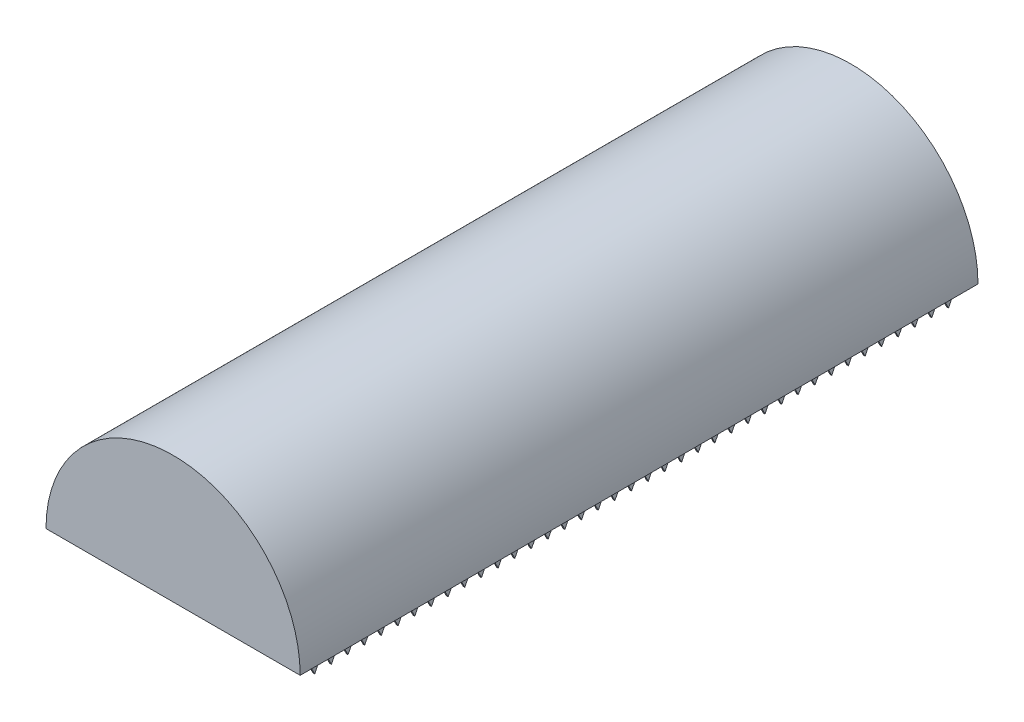
SolidWorks part; units mm, degrees
ref_plane "Front Plane" through (0, 0, 0) normal (0, 0, 1) x (1, 0, 0)
ref_plane "Top Plane" through (0, 0, 0) normal (0, 1, 0) x (1, 0, 0)
ref_plane "Right Plane" through (0, 0, 0) normal (1, 0, 0) x (0, 0, -1)
sketch "Sketch1" plane through (0, 0, 0) normal (0, 0, 1) x (1, 0, 0)
  line L0 (-76.2, 0) -> (76.2, 0)
  arc A0 (-76.2, 0) -> (76.2, 0) centre (0, 0) cw
  dimension "D1" = 76.2
extrude "Boss-Extrude1" add sketch "Sketch1" along normal blind 406.4
shell "Shell1" thickness 6.35 removed face at (0, 0, 203.2)
ref_plane "Plane1" through (69.85, 0, 0) normal (1, 0, 0) x (0, 0, -1)
sketch "Sketch3" plane through (69.85, 0, 0) normal (1, 0, 0) x (0, 0, -1)
  line L0 (-6.35, 0) -> (-11.35, -10)
  line L1 (-11.35, -10) -> (-16.35, 0)
  line L2 (-400.05, 0) -> (-6.35, 0) construction
  line L3 (-11.35, -10) -> (-11.35, 0) construction
  line L4 (-6.35, 0) -> (-16.35, 0) construction
  line L5 (-16.35, 0) -> (-21.35, -10)
  line L6 (-21.35, -10) -> (-26.35, 0)
  line L7 (-16.35, 0) -> (-26.35, 0) construction
  line L8 (-26.35, 0) -> (-31.35, -10)
  line L9 (-31.35, -10) -> (-36.35, 0)
  line L10 (-26.35, 0) -> (-36.35, 0) construction
  line L11 (-36.35, 0) -> (-41.35, -10)
  line L12 (-41.35, -10) -> (-46.35, 0)
  line L13 (-36.35, 0) -> (-46.35, 0) construction
  line L14 (-46.35, 0) -> (-51.35, -10)
  line L15 (-51.35, -10) -> (-56.35, 0)
  line L16 (-46.35, 0) -> (-56.35, 0) construction
  line L17 (-56.35, 0) -> (-61.35, -10)
  line L18 (-61.35, -10) -> (-66.35, 0)
  line L19 (-56.35, 0) -> (-66.35, 0) construction
  line L20 (-66.35, 0) -> (-71.35, -10)
  line L21 (-71.35, -10) -> (-76.35, 0)
  line L22 (-66.35, 0) -> (-76.35, 0) construction
  line L23 (-76.35, 0) -> (-81.35, -10)
  line L24 (-81.35, -10) -> (-86.35, 0)
  line L25 (-76.35, 0) -> (-86.35, 0) construction
  line L26 (-86.35, 0) -> (-91.35, -10)
  line L27 (-91.35, -10) -> (-96.35, 0)
  line L28 (-86.35, 0) -> (-96.35, 0) construction
  line L29 (-96.35, 0) -> (-101.35, -10)
  line L30 (-101.35, -10) -> (-106.35, 0)
  line L31 (-96.35, 0) -> (-106.35, 0) construction
  line L32 (-106.35, 0) -> (-111.35, -10)
  line L33 (-111.35, -10) -> (-116.35, 0)
  line L34 (-106.35, 0) -> (-116.35, 0) construction
  line L35 (-116.35, 0) -> (-121.35, -10)
  line L36 (-121.35, -10) -> (-126.35, 0)
  line L37 (-116.35, 0) -> (-126.35, 0) construction
  line L38 (-126.35, 0) -> (-131.35, -10)
  line L39 (-131.35, -10) -> (-136.35, 0)
  line L40 (-126.35, 0) -> (-136.35, 0) construction
  line L41 (-136.35, 0) -> (-141.35, -10)
  line L42 (-141.35, -10) -> (-146.35, 0)
  line L43 (-136.35, 0) -> (-146.35, 0) construction
  line L44 (-146.35, 0) -> (-151.35, -10)
  line L45 (-151.35, -10) -> (-156.35, 0)
  line L46 (-146.35, 0) -> (-156.35, 0) construction
  line L47 (-156.35, 0) -> (-161.35, -10)
  line L48 (-161.35, -10) -> (-166.35, 0)
  line L49 (-156.35, 0) -> (-166.35, 0) construction
  line L50 (-166.35, 0) -> (-171.35, -10)
  line L51 (-171.35, -10) -> (-176.35, 0)
  line L52 (-166.35, 0) -> (-176.35, 0) construction
  line L53 (-176.35, 0) -> (-181.35, -10)
  line L54 (-181.35, -10) -> (-186.35, 0)
  line L55 (-176.35, 0) -> (-186.35, 0) construction
  line L56 (-186.35, 0) -> (-191.35, -10)
  line L57 (-191.35, -10) -> (-196.35, 0)
  line L58 (-186.35, 0) -> (-196.35, 0) construction
  line L59 (-196.35, 0) -> (-201.35, -10)
  line L60 (-201.35, -10) -> (-206.35, 0)
  line L61 (-196.35, 0) -> (-206.35, 0) construction
  line L62 (-206.35, 0) -> (-211.35, -10)
  line L63 (-211.35, -10) -> (-216.35, 0)
  line L64 (-206.35, 0) -> (-216.35, 0) construction
  line L65 (-216.35, 0) -> (-221.35, -10)
  line L66 (-221.35, -10) -> (-226.35, 0)
  line L67 (-216.35, 0) -> (-226.35, 0) construction
  line L68 (-226.35, 0) -> (-231.35, -10)
  line L69 (-231.35, -10) -> (-236.35, 0)
  line L70 (-226.35, 0) -> (-236.35, 0) construction
  line L71 (-236.35, 0) -> (-241.35, -10)
  line L72 (-241.35, -10) -> (-246.35, 0)
  line L73 (-236.35, 0) -> (-246.35, 0) construction
  line L74 (-246.35, 0) -> (-251.35, -10)
  line L75 (-251.35, -10) -> (-256.35, 0)
  line L76 (-246.35, 0) -> (-256.35, 0) construction
  line L77 (-256.35, 0) -> (-261.35, -10)
  line L78 (-261.35, -10) -> (-266.35, 0)
  line L79 (-256.35, 0) -> (-266.35, 0) construction
  line L80 (-266.35, 0) -> (-271.35, -10)
  line L81 (-271.35, -10) -> (-276.35, 0)
  line L82 (-266.35, 0) -> (-276.35, 0) construction
  line L83 (-276.35, 0) -> (-281.35, -10)
  line L84 (-281.35, -10) -> (-286.35, 0)
  line L85 (-276.35, 0) -> (-286.35, 0) construction
  line L86 (-286.35, 0) -> (-291.35, -10)
  line L87 (-291.35, -10) -> (-296.35, 0)
  line L88 (-286.35, 0) -> (-296.35, 0) construction
  line L89 (-296.35, 0) -> (-301.35, -10)
  line L90 (-301.35, -10) -> (-306.35, 0)
  line L91 (-296.35, 0) -> (-306.35, 0) construction
  line L92 (-306.35, 0) -> (-311.35, -10)
  line L93 (-311.35, -10) -> (-316.35, 0)
  line L94 (-306.35, 0) -> (-316.35, 0) construction
  line L95 (-316.35, 0) -> (-321.35, -10)
  line L96 (-321.35, -10) -> (-326.35, 0)
  line L97 (-316.35, 0) -> (-326.35, 0) construction
  line L98 (-326.35, 0) -> (-331.35, -10)
  line L99 (-331.35, -10) -> (-336.35, 0)
  line L100 (-326.35, 0) -> (-336.35, 0) construction
  line L101 (-336.35, 0) -> (-341.35, -10)
  line L102 (-341.35, -10) -> (-346.35, 0)
  line L103 (-336.35, 0) -> (-346.35, 0) construction
  line L104 (-346.35, 0) -> (-351.35, -10)
  line L105 (-351.35, -10) -> (-356.35, 0)
  line L106 (-346.35, 0) -> (-356.35, 0) construction
  line L107 (-356.35, 0) -> (-361.35, -10)
  line L108 (-361.35, -10) -> (-366.35, 0)
  line L109 (-356.35, 0) -> (-366.35, 0) construction
  line L110 (-366.35, 0) -> (-371.35, -10)
  line L111 (-371.35, -10) -> (-376.35, 0)
  line L112 (-366.35, 0) -> (-376.35, 0) construction
  line L113 (-376.35, 0) -> (-381.35, -10)
  line L114 (-381.35, -10) -> (-386.35, 0)
  line L115 (-376.35, 0) -> (-386.35, 0) construction
  line L116 (-386.35, 0) -> (-391.35, -10)
  line L117 (-391.35, -10) -> (-396.35, 0)
  line L118 (-386.35, 0) -> (-396.35, 0) construction
  line L119 (-396.35, 0) -> (-6.35, 0)
  dimension "D1" = 10
  dimension "D2" = 10
  dimension "D3" = 39
extrude "Boss-Extrude2" add sketch "Sketch3" against normal blind 1 separate body contours L119 L1 L0 | L119 L6 L5 | L119 L9 L8 | L119 L12 L11 | L119 L15 L14 | L119 L18 L17 | L119 L21 L20 | L119 L24 L23 | L119 L27 L26 | L119 L30 L29 | L119 L33 L32 | L119 L36 L35 | L119 L39 L38 | L119 L42 L41 | L119 L45 L44 | L119 L48 L47 | L119 L51 L50 | L119 L54 L53 | L119 L57 L56 | L119 L60 L59 | L119 L63 L62 | L119 L66 L65 | L119 L69 L68 | L119 L72 L71 | L119 L75 L74 | L119 L78 L77 | L119 L81 L80 | L119 L84 L83 | L119 L87 L86 | L119 L90 L89 | L119 L93 L92 | L119 L96 L95 | L119 L99 L98 | L119 L117 L116 | L119 L114 L113 | L119 L111 L110 | L119 L108 L107 | L119 L105 L104 | L119 L102 L101 | L5 L6 L8 L9 L11 L12 L14 L15 L17 L18 L20 L21 L23 L24 L26 L27 L29 L30 L32 L33 L35 L36 L38 L39 L41 L42 L44 L45 L47 L48 L50 L51 L53 L54 L56 L57 L59 L60 L62 L63 L65 L66 L68 L69 L71 L72 L74 L75 L77 L78 L80 L81 L83 L84 L86 L87 L89 L90 L92 L93 L95 L96 L98 L99 L101 L102 L104 L105 L107 L108 L110 L111 L113 L114 L116 L117 L119 L0 L1 region at (69.85, -3.3333, 391.35) region at (69.85, -3.3333, 381.35) region at (69.85, -3.3333, 371.35) region at (69.85, -3.3333, 361.35) region at (69.85, -3.3333, 351.35) region at (69.85, -3.3333, 341.35) region at (69.85, -3.3333, 331.35) region at (69.85, -3.3333, 321.35) region at (69.85, -3.3333, 311.35) region at (69.85, -3.3333, 301.35) region at (69.85, -3.3333, 291.35) region at (69.85, -3.3333, 281.35) region at (69.85, -3.3333, 271.35) region at (69.85, -3.3333, 261.35) region at (69.85, -3.3333, 251.35) region at (69.85, -3.3333, 241.35) region at (69.85, -3.3333, 231.35) region at (69.85, -3.3333, 221.35) region at (69.85, -3.3333, 211.35) region at (69.85, -3.3333, 201.35) region at (69.85, -3.3333, 191.35) region at (69.85, -3.3333, 181.35) region at (69.85, -3.3333, 171.35) region at (69.85, -3.3333, 161.35) region at (69.85, -3.3333, 151.35) region at (69.85, -3.3333, 141.35) region at (69.85, -3.3333, 131.35) region at (69.85, -3.3333, 121.35) region at (69.85, -3.3333, 111.35) region at (69.85, -3.3333, 101.35) region at (69.85, -3.3333, 91.35) region at (69.85, -3.3333, 81.35) region at (69.85, -3.3333, 71.35) region at (69.85, -3.3333, 61.35) region at (69.85, -3.3333, 51.35) region at (69.85, -3.3333, 41.35) region at (69.85, -3.3333, 31.35) region at (69.85, -3.3333, 21.35) region at (69.85, -3.3333, 11.35)
equation "\"1omm\"=9.38487"
